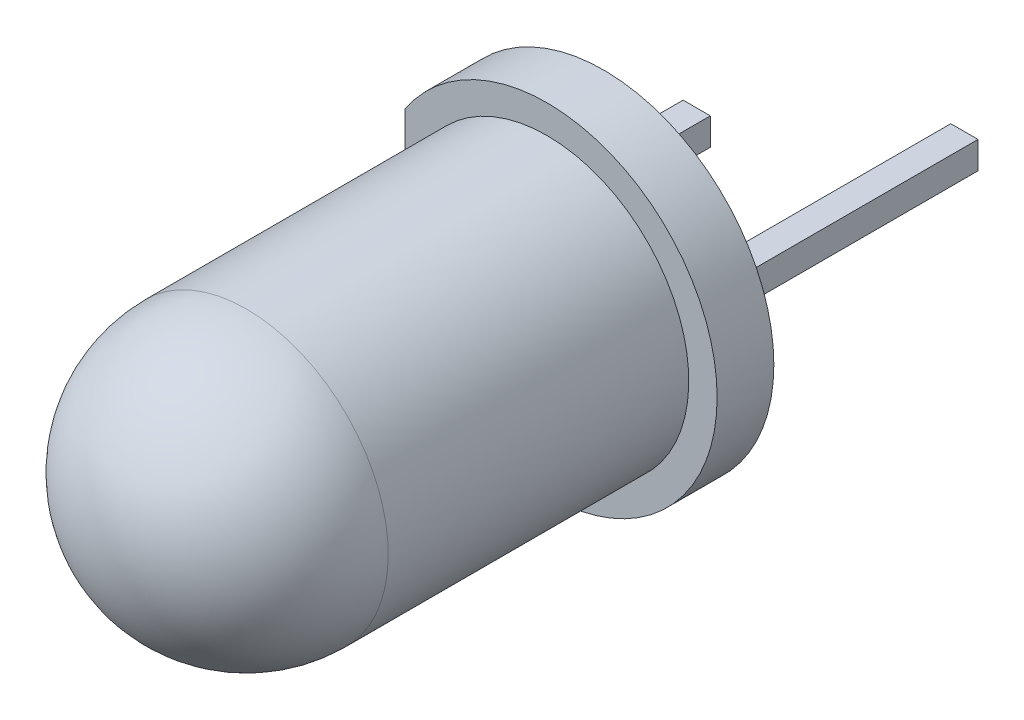
SolidWorks part; units mm, degrees
ref_plane "Plano frontal" through (0, 0, 0) normal (0, 0, 1) x (1, 0, 0)
ref_plane "Plano superior" through (0, 0, 0) normal (0, 1, 0) x (1, 0, 0)
ref_plane "Plano direito" through (0, 0, 0) normal (1, 0, 0) x (0, 0, -1)
sketch "Esboço1" plane through (0, 0, 0) normal (0, 0, 1) x (1, 0, 0)
  circle A0 centre (0, 0) radius 3
  dimension "D1" = 6
extrude "Ressalto-extrusão1" add sketch "Esboço1" along normal blind 1
sketch "Esboço3" plane through (0, 0, 0) normal (1, 0, 0) x (0, 0, -1)
  line L0 (-1, 0) -> (-8.8, 0)
  line L1 (-1, 3) -> (-1, -3) construction
  line L2 (-6.3, 2.5) -> (-1, 2.5)
  line L3 (-1, 0) -> (-1, 2.5)
  arc A0 (-8.8, 0) -> (-6.3, 2.5) centre (-6.3, 0) cw
  dimension "D1" = 2.5
  dimension "D2" = 7.8
revolve "Revolução1" add sketch "Esboço3" angle 360 about L0
sketch "Esboço4" plane through (0, 0, 0) normal (0, 0, -1) x (-1, 0, 0)
  line L0 (2.5, 1.6583) -> (2.5, -1.6583)
  circle A0 centre (0, 0) radius 3 construction
  arc A1 (2.5, -1.6583) -> (2.5, 1.6583) centre (0, 0) ccw
  circle A2 centre (0, 0) radius 2.5 construction
extrude "Corte-extrusão1" cut sketch "Esboço4" against normal up to surface (1 mm away) up to face at (2.5, 0, 1)
sketch "Esboço5" plane through (0, 0, 0) normal (0, 0, -1) x (-1, 0, 0)
  line L0 (-1.12, 0) -> (1.12, 0) construction
  line L1 (-1.6, -0.24) -> (-1.12, -0.24)
  line L2 (-1.6, -0.24) -> (-1.6, 0.24)
  line L3 (-1.6, 0.24) -> (-1.12, 0.24)
  line L4 (-1.12, -0.24) -> (-1.12, 0.24)
  line L5 (1.12, -0.24) -> (1.6, -0.24)
  line L6 (1.12, -0.24) -> (1.12, 0.24)
  line L7 (1.12, 0.24) -> (1.6, 0.24)
  line L8 (1.6, -0.24) -> (1.6, 0.24)
  dimension "D1" = 3.2
  dimension "D2" = 0.48
extrude "Ressalto-extrusão2" add sketch "Esboço5" along normal blind 3 separate body
sketch "Esboço6" plane through (0, 0, -3) normal (0, 0, -1) x (-1, 0, 0)
  line L4 (-1.6, 0.24) -> (-1.6, -0.24)
  line L5 (-1.6, -0.24) -> (-1.12, -0.24)
  line L6 (-1.12, -0.24) -> (-1.12, 0.24)
  line L7 (-1.12, 0.24) -> (-1.6, 0.24)
  line L8 (-1.6, 0.24) -> (-1.6, -0.24)
  line L9 (-1.6, -0.24) -> (-1.12, -0.24)
  line L10 (-1.12, -0.24) -> (-1.12, 0.24)
  line L11 (-1.12, 0.24) -> (-1.6, 0.24)
  dimension "D1" = 0
extrude "Ressalto-extrusão3" add sketch "Esboço6" along normal blind 2 separate body
sketch "Esboço7" plane through (0, 0, 0) normal (0, 1, 0) x (1, 0, 0)
  line L0 (-1.6, 0) -> (-1.6, -3.5)
  line L1 (-1.12, 0) -> (-1.12, -2)
  line L2 (0.02, -2) -> (1.2, -4)
  line L3 (1.2, -4) -> (-1.3, -4)
  line L4 (-1.3, -4) -> (-1.6, -3.5)
  line L5 (-1.12, -2) -> (0.02, -2)
  line L6 (1.6, 0) -> (1.6, -4)
  line L7 (1.6, -4) -> (1.4, -4)
  line L8 (1.4, -4) -> (0.22, -2)
  line L9 (0.22, -2) -> (1.12, -2)
  line L10 (1.12, -2) -> (1.12, 0)
  line L11 (-1.6, 0) -> (-1.12, 0)
  line L12 (1.12, 0) -> (1.6, 0)
  dimension "D1" = 4
  dimension "D2" = 2
  dimension "D3" = 2.8
  dimension "D4" = 0.2
  dimension "D5" = 0.9
  dimension "D6" = 3.5
  dimension "D7" = 2.5
extrude "Corte-extrusão2" cut sketch "Esboço7" against normal mid plane 0.48
sketch "Esboço8" plane through (0, 0, 0) normal (0, 1, 0) x (1, 0, 0)
  line L0 (-1.3, -4) -> (1.2, -4) construction
  line L1 (-1.6, -3.5) -> (-1.3, -4) construction
  line L2 (-1.6, 0) -> (-1.6, -3.5) construction
  line L3 (1.2, -4) -> (0.02, -2) construction
  line L4 (0.02, -2) -> (-1.12, -2) construction
  line L5 (-1.12, -2) -> (-1.12, 0) construction
  line L6 (0.22, -2) -> (1.4, -4) construction
  line L7 (1.12, -2) -> (0.22, -2) construction
  line L8 (1.12, 0) -> (1.12, -2) construction
  line L9 (1.6, -4) -> (1.6, 0) construction
  line L10 (1.4, -4) -> (1.6, -4) construction
  line L11 (-1.12, 0) -> (-1.6, 0) construction
  line L12 (1.6, 0) -> (1.12, 0) construction
  line L13 (-1.3, -4) -> (1.2, -4)
  line L14 (-1.6, -3.5) -> (-1.3, -4)
  line L15 (-1.6, 0) -> (-1.6, -3.5)
  line L16 (1.2, -4) -> (0.02, -2)
  line L17 (0.02, -2) -> (-1.12, -2)
  line L18 (-1.12, -2) -> (-1.12, 0)
  line L19 (0.22, -2) -> (1.4, -4)
  line L20 (1.12, -2) -> (0.22, -2)
  line L21 (1.12, 0) -> (1.12, -2)
  line L22 (1.6, -4) -> (1.6, 0)
  line L23 (1.4, -4) -> (1.6, -4)
  line L24 (-1.12, 0) -> (-1.6, 0)
  line L25 (1.6, 0) -> (1.12, 0)
extrude "Ressalto-extrusão4" add sketch "Esboço8" along normal mid plane 0.48 separate body
combine bodies "Combinar1" operation type add bodies to combine 109 106 104
combine bodies "Combinar2" operation type add bodies to combine 108 105
sketch "Esboço10" plane through (0, 0, 0) normal (0, 1, 0) x (1, 0, 0)
  line L0 (-0.05, -4) -> (-0.05, -3.7)
  line L1 (-1.3, -4) -> (1.2, -4) construction
  line L2 (-0.55, -4) -> (-0.05, -4)
  arc A0 (-0.05, -3.7) -> (-0.55, -4) centre (-0.05, -4.2667) ccw
  dimension "D1" = 0.5
  dimension "D2" = 0.3
revolve "Corte-Revolução1" cut sketch "Esboço10" angle 360 about L0
sketch "Esboço11" plane through (0, 0, 0) normal (0, 1, 0) x (1, 0, 0)
  line L0 (-0.55, -4) -> (-0.05, -4) construction
  line L1 (-0.05, -4) -> (-0.05, -3.7) construction
  line L2 (-0.55, -4) -> (-0.05, -4)
  line L3 (-0.05, -4) -> (-0.05, -3.7)
  arc A0 (-0.05, -3.7) -> (-0.55, -4) centre (-0.05, -4.2667) ccw construction
  arc A1 (-0.05, -3.7) -> (-0.55, -4) centre (-0.05, -4.2667) ccw
revolve "Revolução2" add sketch "Esboço11" angle 360 about L3
combine bodies "Combinar3" operation type add bodies to combine 113 112
sketch "Esboço12" plane through (0, 0, 4) normal (0, 0, 1) x (1, 0, 0)
  circle A0 centre (-0.05, 0) radius 0.2
  arc A1 (0.3886, 0.24) -> (-0.4886, 0.24) centre (-0.05, 0) ccw construction
  dimension "D1" = 0.4
extrude "Corte-extrusão3" cut sketch "Esboço12" against normal blind 0.1
sketch "Esboço13" plane through (0, 0, 0) normal (0, 1, 0) x (1, 0, 0)
  line L0 (1.6, 5) -> (-7.0603, 10)
  line L1 (1.6, 5) -> (1.12, 5) construction
  dimension "D1" = 10
  dimension "D2" = 30
ref_plane "Plano1" through (2.5651, 0, -4.4428) normal (0.5, 0, -0.866) x (-0.866, 0, -0.5)
